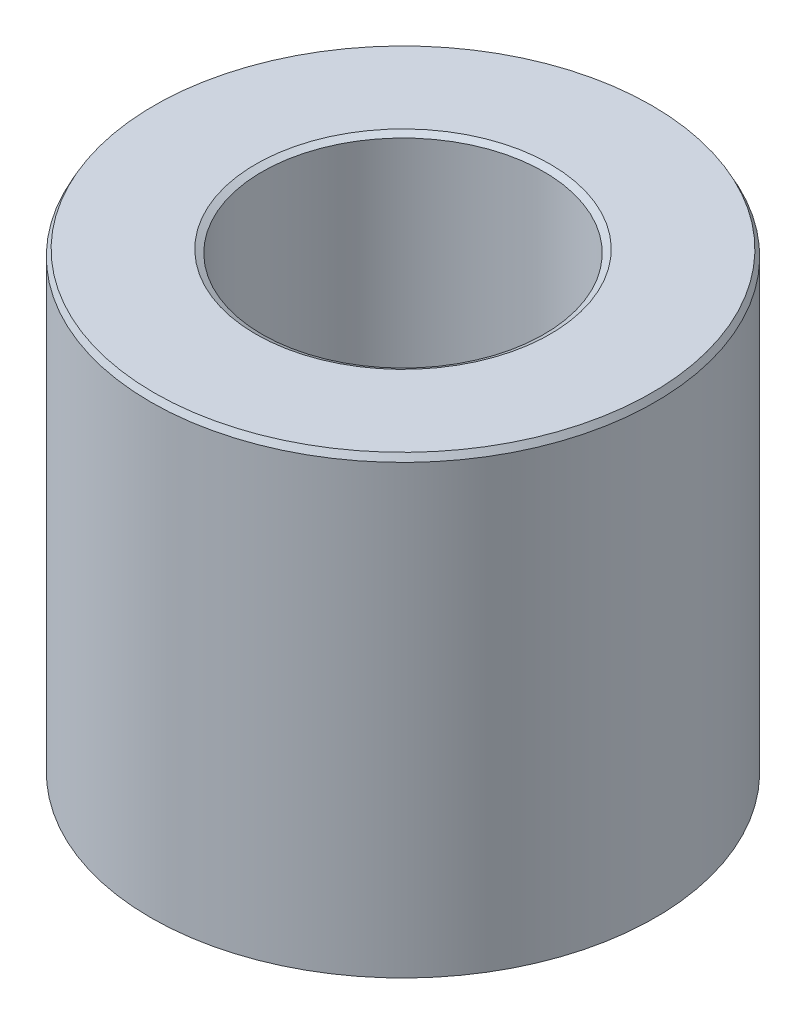
SolidWorks part; units mm, degrees
ref_plane "Front Plane" through (0, 0, 0) normal (0, 0, 1) x (1, 0, 0)
ref_plane "Top Plane" through (0, 0, 0) normal (0, 1, 0) x (1, 0, 0)
ref_plane "Right Plane" through (0, 0, 0) normal (1, 0, 0) x (0, 0, -1)
sketch "Sketch1" plane through (0, 0, 0) normal (0, 1, 0) x (1, 0, 0)
  circle A0 centre (0, 0) radius 25
  dimension "SLEEVE_OD" = 50
extrude "Boss-Extrude1" add sketch "Sketch1" along normal blind 45.2234
sketch "Sketch2" plane through (0, 0, 0) normal (0, 1, 0) x (1, 0, 0)
  circle A0 centre (0, 0) radius 13.9657
  dimension "BORE_D" = 27.9314
extrude "Cut-Extrude1" cut sketch "Sketch2" along normal through all
chamfer "Chamfer1" distance 0.6299 angle 27.995 4 edges at (0, 45.2234, 13.9657) (0, 0, 13.9657) (0, 0, 25) (0, 45.2234, 25) first distance on face at (0, 45.2234, 13.9657) first distance on face at (0, 0, 13.9657) first distance on face at (0, 45.2234, 25)
